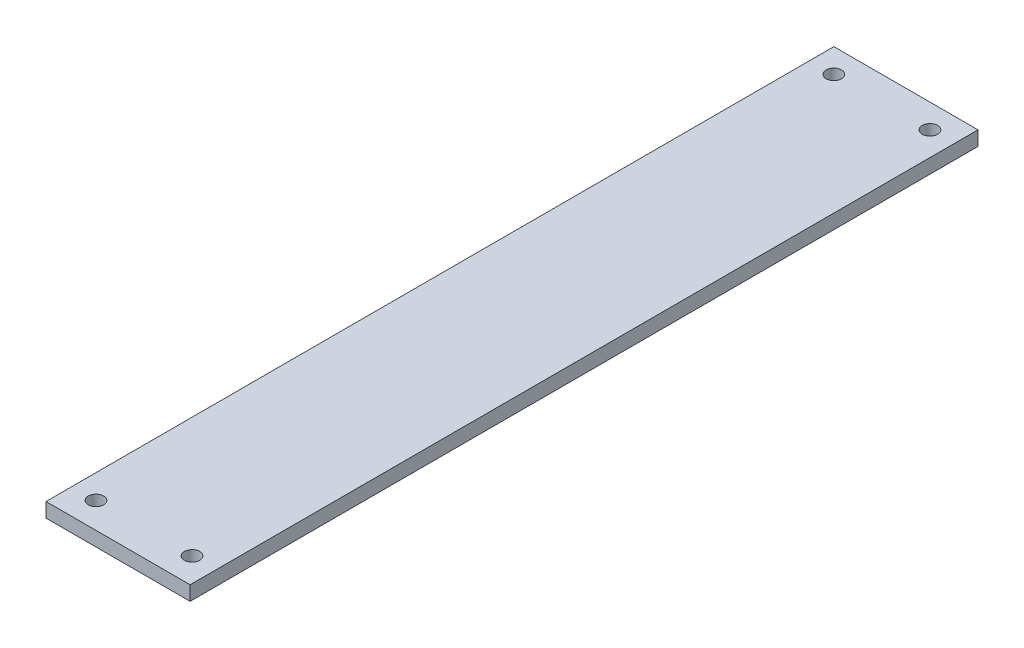
SolidWorks part; units mm, degrees
ref_plane "Front Plane" through (0, 0, 0) normal (0, 0, 1) x (1, 0, 0)
ref_plane "Top Plane" through (0, 0, 0) normal (0, 1, 0) x (1, 0, 0)
ref_plane "Right Plane" through (0, 0, 0) normal (1, 0, 0) x (0, 0, -1)
sketch "Sketch1" plane through (0, 0, 0) normal (0, 1, 0) x (1, 0, 0)
  line L1 (0, 0) -> (30, 0)
  line L2 (0, 0) -> (0, 164)
  line L3 (0, 164) -> (30, 164)
  line L4 (30, 0) -> (30, 164)
  dimension "D1" = 30
  dimension "D2" = 164
extrude "Boss-Extrude1" add sketch "Sketch1" along normal blind 3
sketch "Sketch2" plane through (0, 3, 0) normal (0, 1, 0) x (1, 0, 0)
  line L0 (30, 164) -> (0, 164) construction
  line L1 (30, 0) -> (30, 164) construction
  circle A0 centre (25, 159) radius 1.6
  circle A1 centre (25, 5.4) radius 1.6
  circle A2 centre (5, 159) radius 1.6
  circle A3 centre (5, 5.4) radius 1.6
  point P12 (0, 0)
  point P13 (0, 0)
  dimension "D1" = 3.2
  dimension "D4" = 3.2
  dimension "D2" = 5
  dimension "D3" = 5
  dimension "D5" = 153.6
  dimension "D6" = 5
  dimension "D7" = 20
  dimension "D8" = 20
extrude "Cut-Extrude1" cut sketch "Sketch2" against normal blind 10
